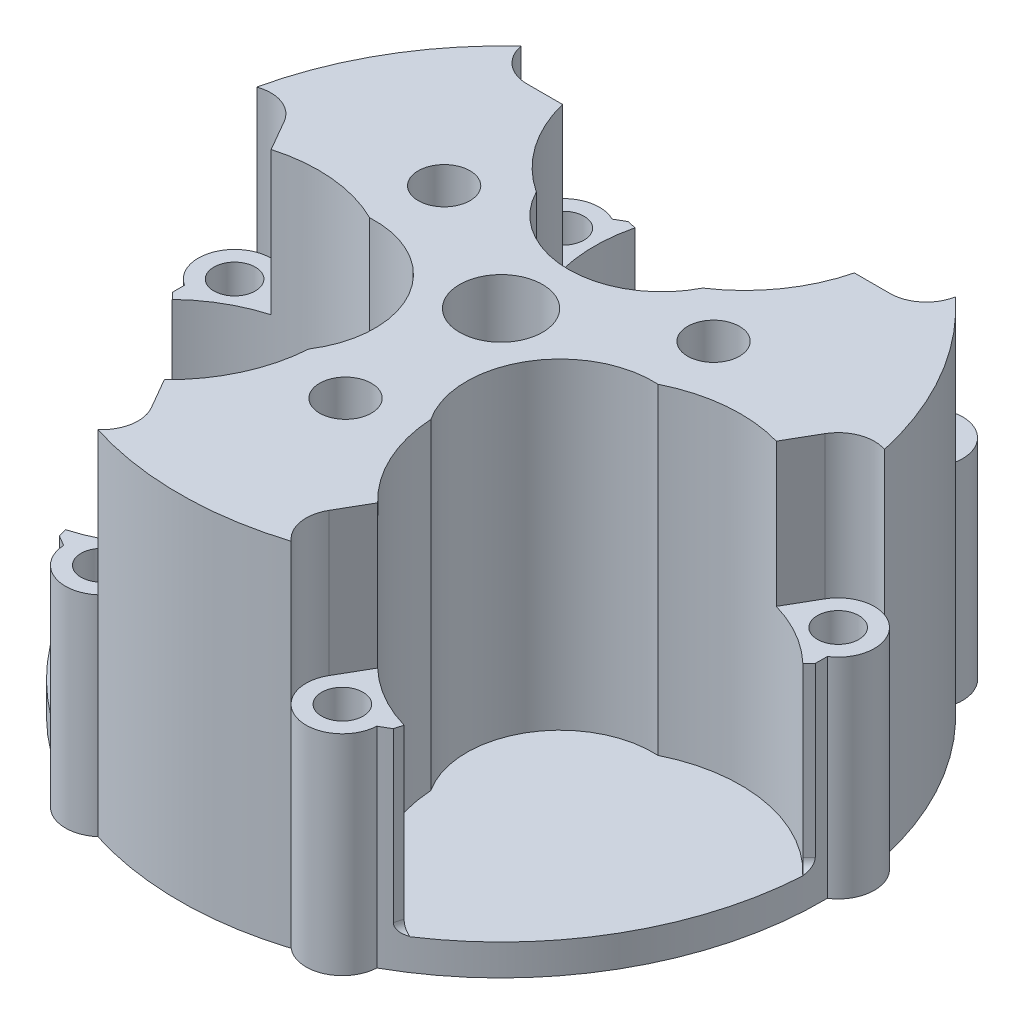
SolidWorks part; units mm, degrees
ref_plane "Front Plane" through (0, 0, 0) normal (0, 0, 1) x (1, 0, 0)
ref_plane "Top Plane" through (0, 0, 0) normal (0, 1, 0) x (1, 0, 0)
ref_plane "Right Plane" through (0, 0, 0) normal (1, 0, 0) x (0, 0, -1)
sketch "Sketch1" plane through (0, 0, 0) normal (0, 1, 0) x (1, 0, 0)
  line L0 (0, 0) -> (0, 23.5) construction
  line L1 (-17.5, 23.5) -> (0, 23.5) construction
  line L2 (0, 23.5) -> (17.5, 23.5) construction
  circle A1 centre (0, 15.5) radius 2.5 construction
  circle A2 centre (13.4234, -7.75) radius 2.5 construction
  circle A3 centre (-13.4234, -7.75) radius 2.5 construction
  arc A4 (-13.8713, 27.7234) -> (13.8713, 27.7234) centre (0, 23.5) ccw
  arc A5 (30.9448, -1.8488) -> (17.0735, -25.8746) centre (20.3516, -11.75) ccw
  arc A6 (-17.0735, -25.8746) -> (-30.9448, -1.8488) centre (-20.3516, -11.75) ccw
  circle A7 centre (17.5, 23.5) radius 2 construction
  circle A8 centre (-17.5, 23.5) radius 2 construction
  arc A24 (-13.8713, 27.7234) -> (-15.8991, 26.6124) centre (0, 0) ccw
  arc A25 (-30.9965, 0.4628) -> (-30.9448, -1.8488) centre (0, 0) ccw
  arc A26 (-15.8991, 26.6124) -> (-20.9406, 22.858) centre (-17.5, 23.5) ccw
  arc A27 (20.9406, 22.858) -> (15.8991, 26.6124) centre (17.5, 23.5) ccw
  arc A32 (-9.2552, -29.5862) -> (9.3253, -29.5641) centre (0, 0) ccw
  arc A33 (15.0293, -27.1131) -> (17.0735, -25.8746) centre (0, 0) ccw
  arc A34 (30.1409, 7.2476) -> (20.9406, 22.858) centre (0, 0) ccw
  arc A35 (15.8991, 26.6124) -> (13.8713, 27.7234) centre (0, 0) ccw
  arc A36 (-20.9406, 22.858) -> (-30.25, 6.7778) centre (0, 0) ccw
  arc A37 (-17.0735, -25.8746) -> (-15.0975, -27.0752) centre (0, 0) ccw
  arc A38 (-13.8713, 27.7234) -> (-30.266, 6.7061) centre (0, 0) ccw
  arc A39 (30.9448, -1.8488) -> (30.9965, 0.4628) centre (0, 0) ccw
  arc A40 (30.9448, -1.8488) -> (30.9965, 0.4628) centre (0, 0) ccw
  arc A41 (-17.0735, -25.8746) -> (-15.0975, -27.0752) centre (0, 0) ccw
  arc A42 (30.9965, 0.4628) -> (30.266, 6.7061) centre (29.1016, 3.4054) ccw
  arc A43 (9.3253, -29.5641) -> (15.0975, -27.0752) centre (11.6016, -26.9054) ccw
  arc A44 (-15.0975, -27.0752) -> (-9.3253, -29.5641) centre (-11.6016, -26.9054) ccw
  arc A45 (-30.266, 6.7061) -> (-30.9965, 0.4628) centre (-29.1016, 3.4054) ccw
  arc A46 (-30.9965, 0.4628) -> (-30.9448, -1.8488) centre (0, 0) ccw
  arc A47 (-9.3253, -29.5641) -> (9.3253, -29.5641) centre (0, 0) ccw
  arc A48 (15.0293, -27.1131) -> (17.0735, -25.8746) centre (0, 0) ccw
  arc A49 (30.266, 6.7061) -> (13.8713, 27.7234) centre (0, 0) ccw
  point P6 (0, 23.5)
  dimension "D3" = 5
  dimension "D6" = 29
  dimension "D10" = 4
  dimension "D11" = 7
  dimension "D12" = 2
  dimension "D13" = 3
  dimension "D14" = 17.5
  dimension "D15" = 4
  dimension "D16" = 15.5
  dimension "D2" = 62
  dimension "D5" = 8
  dimension "D8" = 17.5
  dimension "D4" = 3
  dimension "D7" = 3
  dimension "D9" = 2
extrude "Boss-Extrude1" add sketch "Sketch1" along normal blind 19
sketch "Sketch3" plane through (0, 19, 0) normal (0, 1, 0) x (1, 0, 0)
  line L2 (-17.5, 25.5) -> (-17.5, 25.5881) construction
  line L3 (-17.5, 20) -> (-17.5, 23.5) construction
  line L5 (-17.5, 23.5) -> (-17.5, 27) construction
  line L6 (-17.5, 20) -> (-14.0712, 20)
  line L15 (0, 23.5) -> (0, 27.5279) construction
  line L16 (17.5, 20) -> (14.0712, 20)
  line L17 (26.0705, 5.1554) -> (24.3561, 2.1861)
  line L18 (8.5705, -25.1554) -> (10.2849, -22.1861)
  line L19 (-8.5705, -25.1554) -> (-10.2849, -22.1861)
  line L20 (-26.0705, 5.1554) -> (-24.3561, 2.1861)
  arc A2 (-17.5, 25.5) -> (-17.6347, 25.4955) centre (-17.5, 23.5) ccw
  arc A4 (-15.8991, 26.6124) -> (-17.5, 20) centre (-17.5, 23.5) ccw
  arc A7 (-20.9406, 22.858) -> (-13.8713, 27.7234) centre (0, 0) ccw construction
  circle A8 centre (-17.5, 23.5) radius 2
  circle A9 centre (17.5, 23.5) radius 2
  arc A11 (-17.5, 25.5881) -> (-17.6347, 25.4955) centre (0, 0) ccw
  arc A18 (13.8713, 27.7234) -> (15.8991, 26.6124) centre (0, 0) cw
  arc A19 (15.8991, 26.6124) -> (17.5, 20) centre (17.5, 23.5) cw
  arc A20 (14.0712, 20) -> (13.8713, 27.7234) centre (0, 23.5) ccw
  arc A21 (30.9965, 0.4628) -> (26.0705, 5.1554) centre (29.1016, 3.4054) ccw
  arc A22 (30.9448, -1.8488) -> (24.3561, 2.1861) centre (20.3516, -11.75) ccw
  arc A23 (30.9448, -1.8488) -> (30.9965, 0.4628) centre (0, 0) ccw
  circle A24 centre (29.1016, 3.4054) radius 2
  arc A25 (10.2849, -22.1861) -> (17.0735, -25.8746) centre (20.3516, -11.75) ccw
  arc A26 (17.0735, -25.8746) -> (15.0975, -27.0752) centre (0, 0) cw
  arc A27 (15.0975, -27.0752) -> (8.5705, -25.1554) centre (11.6016, -26.9054) cw
  circle A28 centre (11.6016, -26.9054) radius 2
  arc A29 (-15.0975, -27.0752) -> (-8.5705, -25.1554) centre (-11.6016, -26.9054) ccw
  arc A30 (-17.0735, -25.8746) -> (-10.2849, -22.1861) centre (-20.3516, -11.75) ccw
  arc A31 (-17.0735, -25.8746) -> (-15.0975, -27.0752) centre (0, 0) ccw
  circle A32 centre (-11.6016, -26.9054) radius 2
  arc A33 (9.3253, -29.5641) -> (15.0975, -27.0752) centre (11.6016, -26.9054) ccw
  arc A34 (15.0975, -27.0752) -> (17.0735, -25.8746) centre (0, 0) ccw
  arc A35 (30.9448, -1.8488) -> (17.0735, -25.8746) centre (20.3516, -11.75) ccw
  arc A81 (30.9448, -1.8488) -> (30.9965, 0.4628) centre (0, 0) ccw
  arc A82 (30.9965, 0.4628) -> (30.266, 6.7061) centre (29.1016, 3.4054) ccw
  arc A84 (30.266, 6.7061) -> (20.9406, 22.858) centre (0, 0) ccw
  arc A85 (20.9406, 22.858) -> (15.8991, 26.6124) centre (17.5, 23.5) ccw
  arc A86 (15.8991, 26.6124) -> (13.8713, 27.7234) centre (0, 0) ccw
  arc A87 (-13.8713, 27.7234) -> (13.8713, 27.7234) centre (0, 23.5) ccw
  arc A88 (-13.8713, 27.7234) -> (-15.8991, 26.6124) centre (0, 0) ccw
  arc A89 (-15.8991, 26.6124) -> (-20.9406, 22.858) centre (-17.5, 23.5) ccw
  arc A90 (-20.9406, 22.858) -> (-30.266, 6.7061) centre (0, 0) ccw
  arc A91 (-30.266, 6.7061) -> (-30.9965, 0.4628) centre (-29.1016, 3.4054) ccw
  arc A92 (-30.9965, 0.4628) -> (-30.9448, -1.8488) centre (0, 0) ccw
  arc A93 (-17.0735, -25.8746) -> (-30.9448, -1.8488) centre (-20.3516, -11.75) ccw
  arc A94 (-17.0735, -25.8746) -> (-15.0975, -27.0752) centre (0, 0) ccw
  arc A95 (-15.0975, -27.0752) -> (-9.3253, -29.5641) centre (-11.6016, -26.9054) ccw
  arc A96 (-9.3253, -29.5641) -> (9.3253, -29.5641) centre (0, 0) ccw
  arc A97 (9.3253, -29.5641) -> (15.0975, -27.0752) centre (11.6016, -26.9054) ccw
  arc A98 (15.0975, -27.0752) -> (17.0735, -25.8746) centre (0, 0) ccw
  arc A99 (30.9448, -1.8488) -> (17.0735, -25.8746) centre (20.3516, -11.75) ccw
  arc A100 (30.9448, -1.8488) -> (30.9965, 0.4628) centre (0, 0) ccw
  arc A101 (30.9965, 0.4628) -> (30.266, 6.7061) centre (29.1016, 3.4054) ccw
  arc A102 (30.266, 6.7061) -> (20.9406, 22.858) centre (0, 0) ccw
  arc A103 (20.9406, 22.858) -> (15.8991, 26.6124) centre (17.5, 23.5) ccw
  arc A104 (15.8991, 26.6124) -> (13.8713, 27.7234) centre (0, 0) ccw
  arc A105 (-13.8713, 27.7234) -> (-14.0712, 20) centre (0, 23.5) ccw
  arc A106 (-13.8713, 27.7234) -> (-15.8991, 26.6124) centre (0, 0) ccw
  arc A107 (-15.8991, 26.6124) -> (-20.9406, 22.858) centre (-17.5, 23.5) ccw
  arc A108 (-20.9406, 22.858) -> (-30.266, 6.7061) centre (0, 0) ccw
  arc A109 (-30.266, 6.7061) -> (-30.9965, 0.4628) centre (-29.1016, 3.4054) ccw
  arc A110 (-30.9965, 0.4628) -> (-30.9448, -1.8488) centre (0, 0) ccw
  arc A111 (-17.0735, -25.8746) -> (-30.9448, -1.8488) centre (-20.3516, -11.75) ccw
  arc A112 (-17.0735, -25.8746) -> (-15.0975, -27.0752) centre (0, 0) ccw
  arc A113 (-15.0975, -27.0752) -> (-9.3253, -29.5641) centre (-11.6016, -26.9054) ccw
  arc A114 (-9.3253, -29.5641) -> (9.3253, -29.5641) centre (0, 0) ccw
  arc A115 (-24.3561, 2.1861) -> (-30.9448, -1.8488) centre (-20.3516, -11.75) ccw
  arc A116 (-30.9448, -1.8488) -> (-30.9965, 0.4628) centre (0, 0) cw
  arc A117 (-30.9965, 0.4628) -> (-26.0705, 5.1554) centre (-29.1016, 3.4054) cw
  circle A118 centre (-29.1016, 3.4054) radius 2
  dimension "D2" = 4
  dimension "D3" = 4
  dimension "D1" = 0
  dimension "D5" = 3
extrude "Cut-Extrude1" cut sketch "Sketch3" against normal blind 1.8
sketch "Sketch8" plane through (0, 0, 0) normal (0, -1, 0) x (1, 0, 0)
  arc A18 (-15.0975, 27.0752) -> (-30.9965, -0.4628) centre (0, 0) ccw
  arc A19 (-30.9965, -0.4628) -> (-30.266, -6.7061) centre (-29.1016, -3.4054) ccw construction
  arc A20 (-20.9406, -22.858) -> (-15.8991, -26.6124) centre (-17.5, -23.5) ccw construction
  arc A21 (15.8991, -26.6124) -> (20.9406, -22.858) centre (17.5, -23.5) ccw construction
  arc A22 (30.266, -6.7061) -> (30.9965, -0.4628) centre (29.1016, -3.4054) ccw construction
  arc A23 (15.0975, 27.0752) -> (9.3253, 29.5641) centre (11.6016, 26.9054) ccw construction
  arc A24 (-9.3253, 29.5641) -> (-15.0975, 27.0752) centre (-11.6016, 26.9054) ccw construction
  arc A25 (-30.9965, -0.4628) -> (-30.266, -6.7061) centre (-29.1016, -3.4054) ccw
  arc A26 (-20.9406, -22.858) -> (-15.8991, -26.6124) centre (-17.5, -23.5) ccw
  arc A27 (15.8991, -26.6124) -> (20.9406, -22.858) centre (17.5, -23.5) ccw
  arc A28 (30.266, -6.7061) -> (30.9965, -0.4628) centre (29.1016, -3.4054) ccw
  arc A29 (15.0975, 27.0752) -> (9.3253, 29.5641) centre (11.6016, 26.9054) ccw
  arc A30 (-9.3253, 29.5641) -> (-15.0975, 27.0752) centre (-11.6016, 26.9054) ccw
  arc A31 (9.3253, 29.5641) -> (-9.3253, 29.5641) centre (0, 0) ccw
  arc A32 (30.9965, -0.4628) -> (15.0975, 27.0752) centre (0, 0) ccw
  arc A33 (20.9406, -22.858) -> (30.266, -6.7061) centre (0, 0) ccw
  arc A34 (-15.8991, -26.6124) -> (15.8991, -26.6124) centre (0, 0) ccw
  arc A35 (-30.266, -6.7061) -> (-20.9406, -22.858) centre (0, 0) ccw
extrude "Boss-Extrude2" add sketch "Sketch8" along normal blind 3
sketch "Sketch5" plane through (0, 19, 0) normal (0, 1, 0) x (1, 0, 0)
  line L0 (0, 0) -> (0, -15) construction
  line L1 (0, 0) -> (-12.9904, 7.5) construction
  line L2 (0, 0) -> (12.9904, 7.5) construction
  circle A5 centre (-17.5, 23.5) radius 2 construction
  circle A6 centre (17.5, 23.5) radius 2
  circle A11 centre (-17.5, 23.5) radius 2
  circle A12 centre (0, 0) radius 4
  circle A13 centre (-12.9904, 7.5) radius 2.5
  circle A14 centre (12.9904, 7.5) radius 2.5
  circle A15 centre (0, -15) radius 2.5
  circle A16 centre (29.1016, 3.4054) radius 2 construction
  circle A17 centre (-29.1016, 3.4054) radius 2
  circle A18 centre (-29.1016, 3.4054) radius 2
  circle A19 centre (11.6016, -26.9054) radius 2
  circle A20 centre (11.6016, -26.9054) radius 2
  circle A21 centre (-11.6016, -26.9054) radius 2 construction
  circle A22 centre (29.1016, 3.4054) radius 2
  circle A23 centre (-11.6016, -26.9054) radius 2
  dimension "D1" = 8
  dimension "D4" = 5
  dimension "D2" = 15
  dimension "D6" = 0
  dimension "D7" = 0
  dimension "D3" = 3
  dimension "D5" = 3
extrude "Cut-Extrude2" cut sketch "Sketch5" against normal through all
sketch "Sketch7" plane through (0, 19, 0) normal (0, 1, 0) x (1, 0, 0)
  line L18 (-17.5, 20) -> (-14.0712, 20)
  line L29 (-14.8955, 27.1868) -> (-14.0753, 26.9838)
  line L30 (14.0753, 26.9838) -> (14.8955, 27.1868)
  line L31 (30.4063, -1.3024) -> (30.9922, -0.6935)
  line L32 (16.0967, -26.4933) -> (16.331, -25.6814)
  line L33 (-16.331, -25.6814) -> (-16.0967, -26.4933)
  line L34 (-30.9922, -0.6935) -> (-30.4063, -1.3024)
  arc A1 (-30.9965, 0.4628) -> (-30.9448, -1.8488) centre (0, 0) ccw construction
  arc A2 (-24.3561, 2.1861) -> (-30.9448, -1.8488) centre (-20.3516, -11.75) ccw construction
  arc A4 (-15.8991, 26.6124) -> (-20.9406, 22.858) centre (-17.5, 23.5) ccw
  arc A5 (-20.9406, 22.858) -> (-17.5, 20) centre (-17.5, 23.5) ccw
  arc A6 (-13.8713, 27.7234) -> (-14.0712, 20) centre (0, 23.5) ccw
  arc A7 (-13.8713, 27.7234) -> (-15.8991, 26.6124) centre (0, 0) ccw
  arc A10 (-13.8713, 27.7234) -> (-14.0753, 26.9838) centre (0, 23.5) ccw
  arc A11 (-13.8713, 27.7234) -> (-14.8955, 27.1868) centre (0, 0) ccw
  arc A14 (-17.0735, -25.8746) -> (-10.2849, -22.1861) centre (-20.3516, -11.75) ccw construction
  arc A15 (-17.0735, -25.8746) -> (-15.0975, -27.0752) centre (0, 0) ccw construction
  arc A17 (15.0975, -27.0752) -> (17.0735, -25.8746) centre (0, 0) ccw construction
  arc A18 (30.9448, -1.8488) -> (17.0735, -25.8746) centre (20.3516, -11.75) ccw construction
  arc A19 (10.2849, -22.1861) -> (17.0735, -25.8746) centre (20.3516, -11.75) ccw construction
  arc A21 (-17.0735, -25.8746) -> (-30.9448, -1.8488) centre (-20.3516, -11.75) ccw construction
  arc A23 (30.9448, -1.8488) -> (30.4063, -1.3024) centre (20.3516, -11.75) ccw
  arc A24 (16.331, -25.6814) -> (17.0735, -25.8746) centre (20.3516, -11.75) ccw
  arc A51 (-17.0735, -25.8746) -> (-16.331, -25.6814) centre (-20.3516, -11.75) ccw
  arc A52 (30.9448, -1.8488) -> (24.3561, 2.1861) centre (20.3516, -11.75) ccw construction
  arc A53 (30.9448, -1.8488) -> (30.9965, 0.4628) centre (0, 0) ccw construction
  arc A54 (-30.4063, -1.3024) -> (-30.9448, -1.8488) centre (-20.3516, -11.75) ccw
  arc A56 (15.8991, 26.6124) -> (13.8713, 27.7234) centre (0, 0) ccw construction
  arc A59 (14.0712, 20) -> (13.8713, 27.7234) centre (0, 23.5) ccw construction
  arc A63 (-30.9922, -0.6935) -> (-30.9448, -1.8488) centre (0, 0) ccw
  arc A65 (-30.4063, -1.3024) -> (-30.9448, -1.8488) centre (-20.3516, -11.75) ccw
  arc A96 (-17.0735, -25.8746) -> (-16.331, -25.6814) centre (-20.3516, -11.75) ccw
  arc A97 (-17.0735, -25.8746) -> (-16.0967, -26.4933) centre (0, 0) ccw
  arc A99 (16.0967, -26.4933) -> (17.0735, -25.8746) centre (0, 0) ccw
  arc A100 (16.331, -25.6814) -> (17.0735, -25.8746) centre (20.3516, -11.75) ccw
  arc A104 (30.9448, -1.8488) -> (30.4063, -1.3024) centre (20.3516, -11.75) ccw
  arc A105 (30.9448, -1.8488) -> (30.9922, -0.6935) centre (0, 0) ccw
  arc A107 (14.8955, 27.1868) -> (13.8713, 27.7234) centre (0, 0) ccw
  arc A108 (14.0753, 26.9838) -> (13.8713, 27.7234) centre (0, 23.5) ccw
  dimension "D1" = 0
extrude "Cut-Extrude3" cut sketch "Sketch7" against normal up to surface (19 mm away) contours L34 A63 A54 | A51 A97 L33 | L32 A99 A24 | A23 A105 L31 | A108 L30 A107 | A10 A11 L29 up to face at (0, 0, -20)
sketch "Sketch9" plane through (0, 19, 0) normal (0, 1, 0) x (1, 0, 0)
  line L1 (-26.0705, 5.1554) -> (-24.3561, 2.1861)
  line L3 (-8.5705, -25.1554) -> (-10.2849, -22.1861) construction
  line L5 (10.2849, -22.1861) -> (8.5705, -25.1554) construction
  line L7 (26.0705, 5.1554) -> (24.3561, 2.1861) construction
  line L9 (-26.0705, 5.1554) -> (-24.3561, 2.1861)
  line L11 (-10.2849, -22.1861) -> (-8.5705, -25.1554)
  line L18 (-10.2849, -22.1861) -> (-8.5705, -25.1554)
  line L20 (8.5705, -25.1554) -> (10.2849, -22.1861)
  line L23 (8.5705, -25.1554) -> (10.2849, -22.1861)
  line L24 (24.3561, 2.1861) -> (26.0705, 5.1554)
  line L25 (24.3561, 2.1861) -> (26.0705, 5.1554)
  line L26 (17.5, 20) -> (14.0712, 20)
  line L27 (17.5, 20) -> (14.0712, 20)
  line L28 (-14.0712, 20) -> (-17.5, 20)
  line L29 (-14.0712, 20) -> (-17.5, 20)
  line L31 (-17.5, 20) -> (-14.0712, 20) construction
  line L33 (14.0712, 20) -> (17.5, 20) construction
  line L35 (-24.3561, 2.1861) -> (-26.0705, 5.1554) construction
  line L37 (-8.5705, -25.1554) -> (-10.2849, -22.1861)
  line L39 (10.2849, -22.1861) -> (8.5705, -25.1554)
  line L41 (26.0705, 5.1554) -> (24.3561, 2.1861)
  line L43 (-17.5, 20) -> (-14.0712, 20)
  line L45 (14.0712, 20) -> (17.5, 20)
  line L47 (-24.3561, 2.1861) -> (-26.0705, 5.1554)
  circle A0 centre (0, -15) radius 2.5 construction
  circle A1 centre (12.9904, 7.5) radius 2.5 construction
  circle A2 centre (0, 0) radius 4 construction
  circle A3 centre (-12.9904, 7.5) radius 2.5 construction
  circle A4 centre (0, -15) radius 2.5
  circle A5 centre (12.9904, 7.5) radius 2.5
  circle A6 centre (0, 0) radius 4
  circle A7 centre (-12.9904, 7.5) radius 2.5
  arc A10 (-20.9406, 22.858) -> (-30.266, 6.7061) centre (0, 0) ccw
  arc A11 (-20.9406, 22.858) -> (-30.266, 6.7061) centre (0, 0) ccw
  arc A14 (-9.3253, -29.5641) -> (-8.5705, -25.1554) centre (-11.6016, -26.9054) ccw construction
  arc A18 (8.5705, -25.1554) -> (9.3253, -29.5641) centre (11.6016, -26.9054) ccw construction
  arc A37 (30.266, 6.7061) -> (26.0705, 5.1554) centre (29.1016, 3.4054) ccw construction
  arc A38 (-10.2849, -22.1861) -> (-24.3561, 2.1861) centre (-20.3516, -11.75) ccw
  arc A39 (-10.2849, -22.1861) -> (-24.3561, 2.1861) centre (-20.3516, -11.75) ccw
  arc A40 (-9.3253, -29.5641) -> (9.3253, -29.5641) centre (0, 0) ccw
  arc A41 (-9.3253, -29.5641) -> (9.3253, -29.5641) centre (0, 0) ccw
  arc A42 (24.3561, 2.1861) -> (10.2849, -22.1861) centre (20.3516, -11.75) ccw
  arc A43 (24.3561, 2.1861) -> (10.2849, -22.1861) centre (20.3516, -11.75) ccw
  arc A44 (30.266, 6.7061) -> (20.9406, 22.858) centre (0, 0) ccw
  arc A45 (30.266, 6.7061) -> (20.9406, 22.858) centre (0, 0) ccw
  arc A46 (-14.0712, 20) -> (14.0712, 20) centre (0, 23.5) ccw
  arc A47 (-14.0712, 20) -> (14.0712, 20) centre (0, 23.5) ccw
  arc A54 (-26.0705, 5.1554) -> (-30.266, 6.7061) centre (-29.1016, 3.4054) ccw
  arc A56 (-26.0705, 5.1554) -> (-30.266, 6.7061) centre (-29.1016, 3.4054) ccw
  arc A58 (-9.3253, -29.5641) -> (-8.5705, -25.1554) centre (-11.6016, -26.9054) ccw
  arc A60 (-9.3253, -29.5641) -> (-8.5705, -25.1554) centre (-11.6016, -26.9054) ccw
  arc A63 (8.5705, -25.1554) -> (9.3253, -29.5641) centre (11.6016, -26.9054) ccw
  arc A65 (8.5705, -25.1554) -> (9.3253, -29.5641) centre (11.6016, -26.9054) ccw
  arc A67 (30.266, 6.7061) -> (26.0705, 5.1554) centre (29.1016, 3.4054) ccw
  arc A69 (30.266, 6.7061) -> (26.0705, 5.1554) centre (29.1016, 3.4054) ccw
  arc A71 (17.5, 20) -> (20.9406, 22.858) centre (17.5, 23.5) ccw
  arc A73 (17.5, 20) -> (20.9406, 22.858) centre (17.5, 23.5) ccw
  arc A74 (-20.9406, 22.858) -> (-17.5, 20) centre (-17.5, 23.5) ccw
  arc A75 (-20.9406, 22.858) -> (-17.5, 20) centre (-17.5, 23.5) ccw
  arc A78 (-20.9406, 22.858) -> (-17.5, 20) centre (-17.5, 23.5) ccw construction
  arc A81 (17.5, 20) -> (20.9406, 22.858) centre (17.5, 23.5) ccw construction
  arc A86 (-26.0705, 5.1554) -> (-30.266, 6.7061) centre (-29.1016, 3.4054) ccw construction
  arc A91 (-9.3253, -29.5641) -> (-8.5705, -25.1554) centre (-11.6016, -26.9054) ccw
  arc A94 (8.5705, -25.1554) -> (9.3253, -29.5641) centre (11.6016, -26.9054) ccw
  arc A99 (30.266, 6.7061) -> (26.0705, 5.1554) centre (29.1016, 3.4054) ccw
  arc A102 (-20.9406, 22.858) -> (-17.5, 20) centre (-17.5, 23.5) ccw
  arc A105 (17.5, 20) -> (20.9406, 22.858) centre (17.5, 23.5) ccw
  arc A110 (-26.0705, 5.1554) -> (-30.266, 6.7061) centre (-29.1016, 3.4054) ccw
  circle M19 centre (0, 0) radius 4
  circle M20 centre (-12.9904, 7.5) radius 2.5
  circle M21 centre (12.9904, 7.5) radius 2.5
  circle M22 centre (0, -15) radius 2.5
  arc M25 (-20.9406, 22.858) -> (-30.266, 6.7061) centre (0, 0) ccw
  arc M28 (-24.3561, 2.1861) -> (-10.2849, -22.1861) centre (-20.3516, -11.75) cw
  arc M31 (-9.3253, -29.5641) -> (9.3253, -29.5641) centre (0, 0) ccw
  arc M34 (10.2849, -22.1861) -> (24.3561, 2.1861) centre (20.3516, -11.75) cw
  arc M37 (30.266, 6.7061) -> (20.9406, 22.858) centre (0, 0) ccw
  arc M40 (14.0712, 20) -> (-14.0712, 20) centre (0, 23.5) cw
  arc M103 (-30.266, 6.7061) -> (-26.0705, 5.1554) centre (-29.1016, 3.4054) cw
  line M104 (-26.0705, 5.1554) -> (-24.3561, 2.1861)
  line M105 (-10.2849, -22.1861) -> (-8.5705, -25.1554)
  arc M106 (-8.5705, -25.1554) -> (-9.3253, -29.5641) centre (-11.6016, -26.9054) cw
  arc M107 (9.3253, -29.5641) -> (8.5705, -25.1554) centre (11.6016, -26.9054) cw
  line M108 (8.5705, -25.1554) -> (10.2849, -22.1861)
  line M109 (24.3561, 2.1861) -> (26.0705, 5.1554)
  arc M110 (26.0705, 5.1554) -> (30.266, 6.7061) centre (29.1016, 3.4054) cw
  arc M111 (20.9406, 22.858) -> (17.5, 20) centre (17.5, 23.5) cw
  line M112 (17.5, 20) -> (14.0712, 20)
  line M113 (-14.0712, 20) -> (-17.5, 20)
  arc M114 (-17.5, 20) -> (-20.9406, 22.858) centre (-17.5, 23.5) cw
  dimension "D1" = 0
extrude "Boss-Extrude3" add sketch "Sketch9" along normal blind 12 contours M114 M25 M103 M104 M28 M105 M106 M31 M107 M108 M34 M109 M110 M37 M111 M112 M40 M113 M22 M20 M21 M19
sketch "Sketch14" plane through (0, 31, 0) normal (0, 1, 0) x (1, 0, 0)
  line L0 (0, 0) -> (0, 15.5) construction
  arc A0 (-8.023, 11.4219) -> (8.023, 11.4219) centre (0, 15.5) ccw
  arc A1 (-14.0712, 20) -> (14.0712, 20) centre (0, 23.5) ccw construction
  arc A2 (-8.023, 11.4219) -> (8.023, 11.4219) centre (0, 23.5) ccw
  arc A3 (13.9031, 1.2372) -> (5.8801, -12.6591) centre (20.3516, -11.75) ccw
  arc A4 (13.9031, 1.2372) -> (5.8801, -12.6591) centre (13.4234, -7.75) ccw
  arc A5 (-5.8801, -12.6591) -> (-13.9031, 1.2372) centre (-20.3516, -11.75) ccw
  arc A6 (-5.8801, -12.6591) -> (-13.9031, 1.2372) centre (-13.4234, -7.75) ccw
  dimension "D2" = 18
  dimension "D1" = 15.5
  dimension "D3" = 3
extrude "Cut-Extrude4" cut sketch "Sketch14" against normal up to surface (31 mm away) contours A5 A6 | A3 A4 | A2 A0 up to face at (-20.3885, 0, 11.7713)
fillet "Fillet1" radius 1 6 edges at (14.4854, 0, -27.0853) (-14.4854, 0, -27.0853) (16.2139, 0, 26.0874) (30.6993, 0, 0.9979) (-16.2139, 0, 26.0874) (-30.6993, 0, 0.9979)
